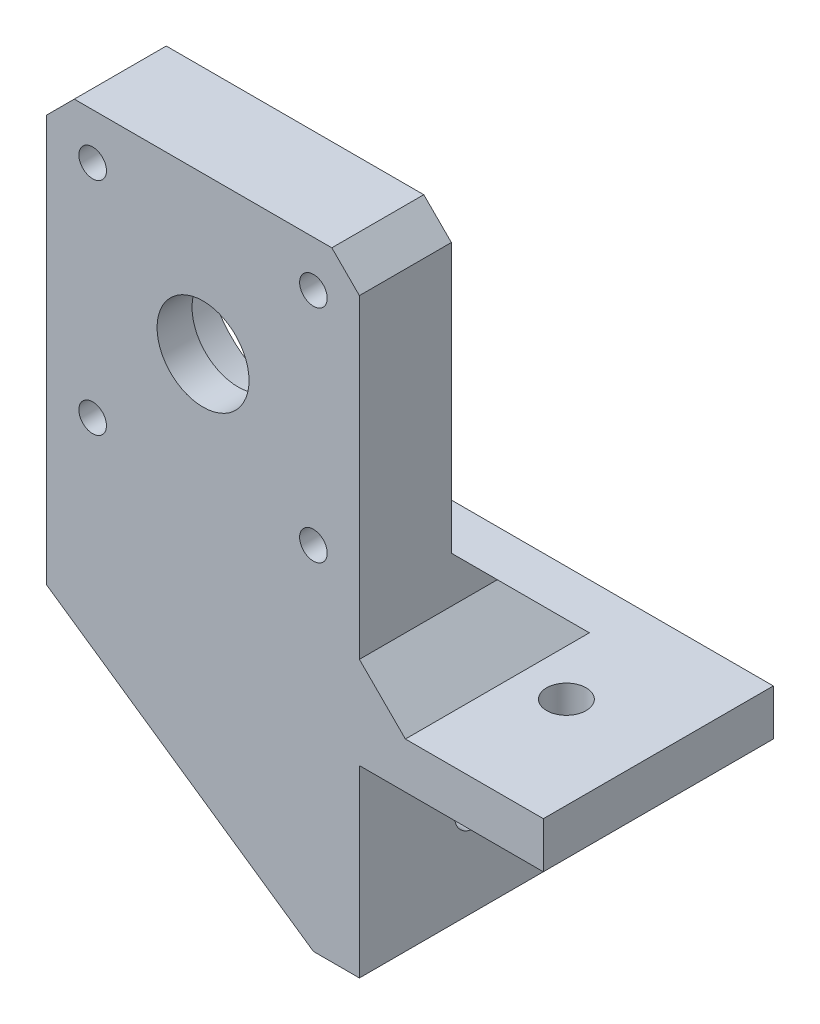
SolidWorks part; units mm, degrees
ref_plane "前视基准面" through (0, 0, 0) normal (0, 0, 1) x (1, 0, 0)
ref_plane "上视基准面" through (0, 0, 0) normal (0, 1, 0) x (1, 0, 0)
ref_plane "右视基准面" through (0, 0, 0) normal (1, 0, 0) x (0, 0, -1)
sketch "草图1" plane through (0, 0, 0) normal (0, 0, 1) x (1, 0, 0)
  line L0 (0, 0) -> (0, 20)
  line L1 (0, 20) -> (20, 20)
  line L2 (20, 20) -> (20, 25)
  line L3 (20, 25) -> (0, 25)
  line L4 (0, 25) -> (0, 67.25)
  line L5 (0, 67.25) -> (-34, 67.25)
  line L6 (-34, 67.25) -> (-34, 20)
  line L7 (-34, 20) -> (-5, 20)
  line L8 (-5, 20) -> (-5, 0)
  line L9 (-5, 0) -> (0, 0)
  circle A0 centre (-17, 50.25) radius 5
  circle A1 centre (-29, 62.25) radius 1.5
  circle A2 centre (-5, 62.25) radius 1.5
  circle A3 centre (-29, 38.25) radius 1.5
  circle A4 centre (-5, 38.25) radius 1.5
  dimension "D3" = 10
  dimension "D13" = 3
  dimension "D1" = 20
  dimension "D2" = 20
  dimension "D4" = 12
  dimension "D5" = 12
  dimension "D6" = 12
  dimension "D7" = 12
  dimension "D8" = 12
  dimension "D9" = 5
  dimension "D10" = 5
  dimension "D11" = 30.25
  dimension "D12" = 12
  dimension "D14" = 5
  dimension "D15" = 5
  dimension "D16" = 5
extrude "凸台-拉伸1" add sketch "草图1" along normal blind 25
sketch "草图2" plane through (0, 0, 0) normal (1, 0, 0) x (0, 0, -1)
  line L0 (-25, 0) -> (0, 0) construction
  circle A0 centre (-12.5, 10) radius 2.15
  point P4 (-12.5, 0)
  dimension "D2" = 4.3
  dimension "D1" = 10
extrude "切除-拉伸1" cut sketch "草图2" against normal blind 30
sketch "草图3" plane through (0, 20, 0) normal (0, -1, 0) x (1, 0, 0)
  line L0 (20, 25) -> (20, 0) construction
  circle A0 centre (10, 12.5) radius 2.15
  point P4 (20, 12.5)
  dimension "D2" = 4.3
  dimension "D1" = 10
extrude "切除-拉伸2" cut sketch "草图3" against normal blind 30
sketch "草图4" plane through (0, 0, 0) normal (0, 0, -1) x (-1, 0, 0)
  line L0 (34, 67.25) -> (34, 20) construction
  line L1 (0, 67.25) -> (34, 67.25)
  line L2 (0, 67.25) -> (0, 25)
  line L3 (0, 25) -> (34, 25)
  line L4 (34, 67.25) -> (34, 25)
  line L6 (-20, 25) -> (0, 25) construction
extrude "切除-拉伸3" cut sketch "草图4" against normal blind 15
chamfer "倒角1" distance 5 angle 45 2 edges at (-5, 20, 12.5) (0, 25, 20)
chamfer "倒角2" distance 3 angle 45 2 edges at (-34, 67.25, 20) (0, 67.25, 20)
sketch "草图6" plane through (0, 0, 15) normal (0, 0, -1) x (-1, 0, 0)
  circle A0 centre (17, 50.25) radius 9.75
  dimension "D1" = 19.5
extrude "切除-拉伸5" cut sketch "草图6" against normal blind 6.2
sketch "草图7" plane through (0, 0, 25) normal (0, 0, 1) x (1, 0, 0)
  line L0 (-34, 20) -> (-10, 20)
  line L1 (-10, 20) -> (-5, 15)
  line L2 (-5, 15) -> (-5, 0)
  line L3 (-5, 0) -> (-34, 20)
extrude "凸台-拉伸2" add sketch "草图7" against normal blind 5
chamfer "倒角3" distance 10 angle 45 1 edges at (-14.5, 25, 15)
